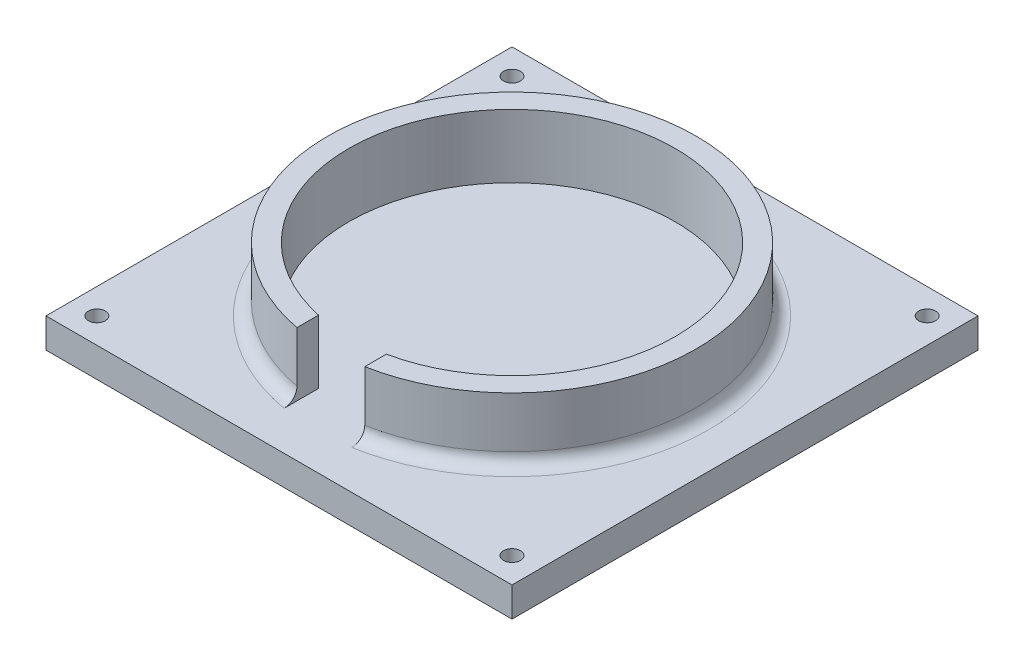
SolidWorks part; units mm, degrees
ref_plane "Plan de face" through (0, 0, 0) normal (0, 0, 1) x (1, 0, 0)
ref_plane "Plan de dessus" through (0, 0, 0) normal (0, 1, 0) x (1, 0, 0)
ref_plane "Plan de droite" through (0, 0, 0) normal (1, 0, 0) x (0, 0, -1)
sketch "Esquisse1" plane through (0, 0, 0) normal (0, 1, 0) x (1, 0, 0)
  line L0 (-26.5217, 31.7252) -> (-26.5217, -78.2748)
  line L1 (-26.5217, -78.2748) -> (83.4783, -78.2748)
  line L2 (83.4783, -78.2748) -> (83.4783, 31.7252)
  line L3 (83.4783, 31.7252) -> (-26.5217, 31.7252)
  dimension "D1" = 110
  dimension "D2" = 110
extrude "Boss.-Extru.1" add sketch "Esquisse1" along normal blind 7
sketch "Esquisse2" plane through (0, 7, 0) normal (0, 1, 0) x (1, 0, 0)
  line L1 (-26.5217, 31.7252) -> (-26.5217, -78.2748) construction
  line L2 (83.4783, 31.7252) -> (-26.5217, 31.7252) construction
  circle A0 centre (28.4783, -23.2748) radius 38.5
  circle A1 centre (28.4783, -23.2748) radius 43.5
  dimension "D1" = 77
  dimension "D4" = 87
  dimension "D2" = 55
  dimension "D3" = 55
extrude "Boss.-Extru.2" add sketch "Esquisse2" along normal blind 15
sketch "Esquisse3" plane through (0, 0, 78.2748) normal (0, 0, 1) x (1, 0, 0)
  line L0 (20.4783, 7) -> (36.4783, 7)
  line L1 (-26.5217, 7) -> (83.4783, 7) construction
  line L2 (36.4783, 7) -> (36.4783, 27)
  line L3 (36.4783, 27) -> (20.4783, 27)
  line L4 (20.4783, 27) -> (20.4783, 7)
  line L5 (83.4783, 7) -> (83.4783, 0) construction
  dimension "D1" = 16
  dimension "D2" = 20
  dimension "D3" = 47
extrude "Enlèv. mat.-Extru.1" cut sketch "Esquisse3" against normal blind 22
sketch "Esquisse4" plane through (0, 7, 0) normal (0, 1, 0) x (1, 0, 0)
  line L0 (-26.5217, 31.7252) -> (-26.5217, -78.2748) construction
  line L1 (-26.5217, -78.2748) -> (83.4783, -78.2748) construction
  line L2 (83.4783, 31.7252) -> (-26.5217, 31.7252) construction
  line L3 (83.4783, -78.2748) -> (83.4783, 31.7252) construction
  circle A0 centre (-20.5217, -72.2748) radius 2
  circle A1 centre (-20.5217, 25.7252) radius 2
  circle A2 centre (77.4783, 25.7252) radius 2
  circle A3 centre (77.4783, -72.2748) radius 2
  dimension "D1" = 4
  dimension "D4" = 4
  dimension "D7" = 4
  dimension "D10" = 4
  dimension "D2" = 6
  dimension "D3" = 6
  dimension "D5" = 6
  dimension "D6" = 6
  dimension "D8" = 6
  dimension "D9" = 6
  dimension "D11" = 6
  dimension "D12" = 6
extrude "Enlèv. mat.-Extru.2" cut sketch "Esquisse4" against normal through all
fillet "Congé1" radius 3 1 edges at (28.4783, 7, -20.2252)
